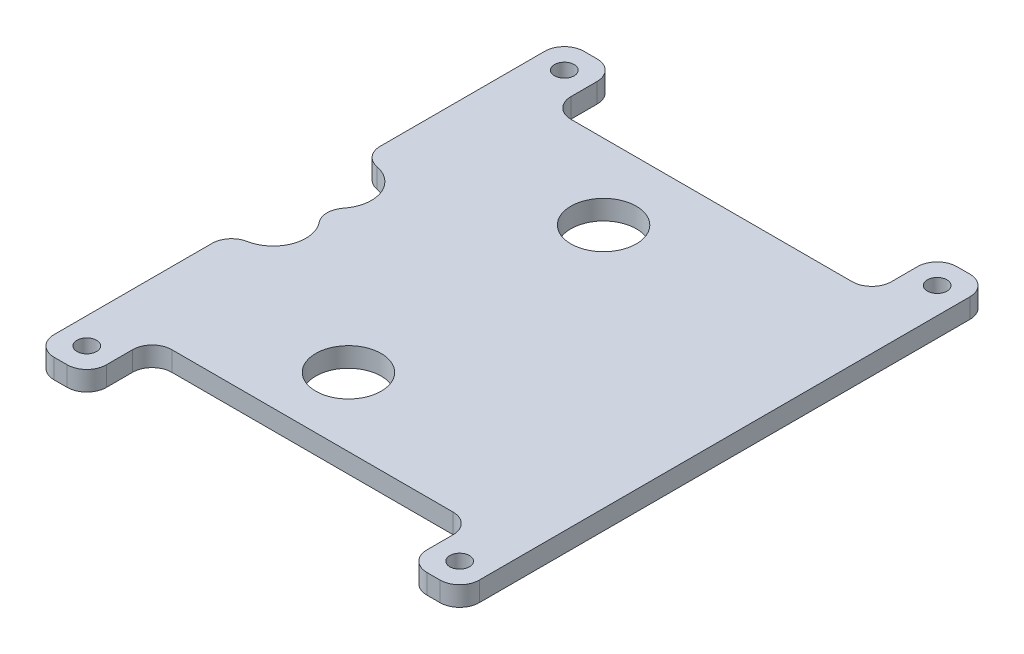
SolidWorks part; units mm, degrees
ref_plane "Спереди" through (0, 0, 0) normal (0, 0, 1) x (1, 0, 0)
ref_plane "Сверху" through (0, 0, 0) normal (0, 1, 0) x (1, 0, 0)
ref_plane "Справа" through (0, 0, 0) normal (1, 0, 0) x (0, 0, -1)
sketch "Sketch1" plane through (0, 0, 0) normal (0, 1, 0) x (1, 0, 0)
  line L0 (10.9056, 0) -> (18.9056, 0) construction
  line L1 (10.9056, 39.7697) -> (10.9056, 61)
  line L2 (18.9056, 0) -> (67.9056, 0)
  line L3 (10.9056, 0) -> (10.9056, 20.2303)
  line L4 (18.9056, 61) -> (67.9056, 61)
  line L5 (75.9056, 0) -> (75.9056, 61)
  line L7 (75.9056, 30.5) -> (18.9056, 30.5) construction
  line L8 (18.9056, 61) -> (18.9056, 71)
  line L9 (10.9056, 0) -> (10.9056, -10)
  line L10 (10.9056, -10) -> (18.9056, -10)
  line L11 (18.9056, 0) -> (18.9056, -10)
  line L12 (14.9056, -6) -> (14.9056, -10) construction
  line L13 (10.9056, 71) -> (18.9056, 71)
  line L14 (10.9056, 61) -> (10.9056, 71)
  line L15 (10.9056, 61) -> (18.9056, 61) construction
  line L17 (75.9056, -2) -> (10.9056, -2) construction
  line L18 (67.9056, 0) -> (75.9056, 0) construction
  line L19 (75.9056, 0) -> (75.9056, -10)
  line L20 (75.9056, -10) -> (67.9056, -10)
  line L21 (67.9056, 0) -> (67.9056, -10)
  line L22 (71.9056, -10) -> (71.9056, -6) construction
  line L23 (14.9056, -6) -> (71.9056, -6) construction
  line L24 (75.9056, 61) -> (75.9056, 71)
  line L25 (75.9056, 71) -> (67.9056, 71)
  line L26 (67.9056, 61) -> (67.9056, 71)
  line L27 (67.9056, 61) -> (75.9056, 61) construction
  circle A0 centre (38.4056, 10.5) radius 5
  circle A1 centre (38.4056, 49.5) radius 5
  arc A2 (12.4056, 30) -> (10.9056, 39.7697) centre (12.4056, 35) ccw
  arc A3 (10.9056, 20.2303) -> (12.4056, 30) centre (12.4056, 25) ccw
  circle A4 centre (14.9056, -6) radius 1.5
  circle A5 centre (14.9056, 67) radius 1.5
  circle A6 centre (71.9056, -6) radius 1.5
  circle A7 centre (71.9056, 67) radius 1.5
  point P0 (0, 0)
  dimension "D1" = 10
  dimension "D2" = 3
  dimension "D3" = 8
  dimension "D4" = 4
  dimension "D5" = 4
extrude "Boss-Extrude1" add sketch "Sketch1" along normal blind 3
fillet "Fillet1" radius 3 15 edges at (75.9056, 1.5, 10) (67.9056, 1.5, 10) (67.9056, 1.5, 0) (18.9056, 1.5, 0) (18.9056, 1.5, 10) (10.9056, 1.5, 10) (10.9056, 1.5, -20.2303) (12.4056, 1.5, -30) (10.9056, 1.5, -39.7697) (10.9056, 1.5, -71) (18.9056, 1.5, -71) (18.9056, 1.5, -61) (67.9056, 1.5, -61) (67.9056, 1.5, -71) (75.9056, 1.5, -71)
